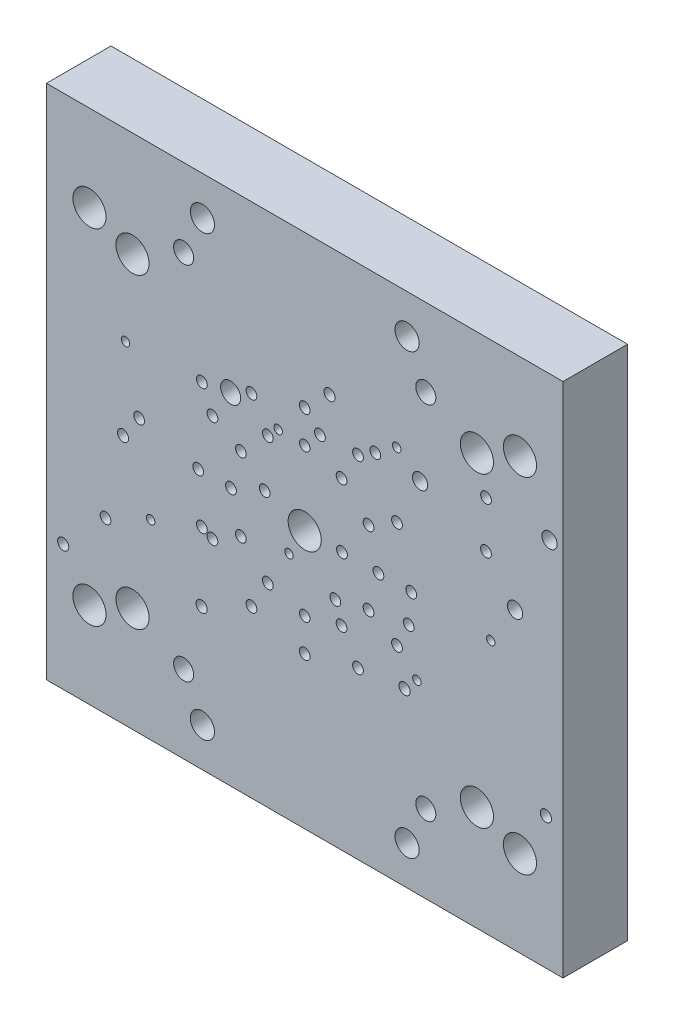
SolidWorks part; units mm, degrees
ref_plane "Front Plane" through (0, 0, 0) normal (0, 0, 1) x (1, 0, 0)
ref_plane "Top Plane" through (0, 0, 0) normal (0, 1, 0) x (1, 0, 0)
ref_plane "Right Plane" through (0, 0, 0) normal (1, 0, 0) x (0, 0, -1)
sketch "Sketch1" plane through (0, 0, 0) normal (0, 0, 1) x (1, 0, 0)
  line L1 (-152.4, 152.4) -> (152.4, 152.4)
  line L2 (-152.4, 152.4) -> (-152.4, -152.4)
  line L3 (-152.4, -152.4) -> (152.4, -152.4)
  line L4 (152.4, 152.4) -> (152.4, -152.4)
  line L5 (-152.4, 152.4) -> (152.4, -152.4) construction
  line L6 (-152.4, -152.4) -> (152.4, 152.4) construction
  point P0 (0, 0)
  dimension "D1" = 304.8
  dimension "D2" = 304.8
extrude "Boss-Extrude1" add sketch "Sketch1" along normal blind 38.1
sketch "Sketch2" plane through (0, 0, 38.1) normal (0, 0, 1) x (1, 0, 0)
  line L0 (-152.4, 0) -> (152.4, 0) construction
  line L5 (-152.4, 152.4) -> (-152.4, -152.4) construction
  line L6 (152.4, -152.4) -> (152.4, 152.4) construction
  line L7 (-152.4, -101.6) -> (152.4, -101.6) construction
  line L8 (-152.4, 101.6) -> (152.4, 101.6) construction
  line L9 (0, 101.6) -> (0, -101.6) construction
  line L10 (127, 101.6) -> (127, -101.6) construction
  line L11 (-127, 101.6) -> (-127, -101.6) construction
  circle A0 centre (-127, 101.6) radius 6.5151
  circle A1 centre (127, 101.6) radius 6.5151
  circle A2 centre (127, -101.6) radius 6.5151
  circle A3 centre (-127, -101.6) radius 6.5151
  circle A4 centre (0, 0) radius 6.5151
  dimension "D5" = 13.0302
  dimension "D1" = 101.6
  dimension "D2" = 101.6
  dimension "D3" = 127
  dimension "D4" = 127
extrude "HAAS T-Slot Holes" cut sketch "Sketch2" against normal through all
sketch "Sketch3" plane through (0, 0, 38.1) normal (0, 0, 1) x (1, 0, 0)
  circle A0 centre (-127, 101.6) radius 9.779
  circle A1 centre (127, 101.6) radius 9.779
  circle A2 centre (0, 0) radius 9.779
  circle A3 centre (127, -101.6) radius 9.779
  circle A4 centre (-127, -101.6) radius 9.779
  dimension "D1" = 19.558
extrude "HAAS Counter Bores" cut sketch "Sketch3" against normal offset from surface (22.225 mm away) 15.875 contours A0 | A1 | A2 | A3 | A4 up to face at (6.5151, 0, 0)
sketch "Sketch4" plane through (0, 0, 38.1) normal (0, 0, 1) x (1, 0, 0)
  line L0 (-127, 90.4875) -> (127, 90.4875) construction
  line L1 (-127, 30.1625) -> (127, 30.1625) construction
  line L2 (-127, 30.1625) -> (-127, -30.1625) construction
  line L3 (-127, -30.1625) -> (127, -30.1625) construction
  line L4 (127, 30.1625) -> (127, -30.1625) construction
  line L5 (-127, 30.1625) -> (127, -30.1625) construction
  line L6 (-127, -30.1625) -> (127, 30.1625) construction
  line L7 (-127, -90.4875) -> (127, -90.4875) construction
  line L8 (-101.6, 90.4875) -> (-101.6, 84.1375) construction
  line L9 (-101.6, -90.4875) -> (-101.6, -84.1375) construction
  line L10 (101.6, -90.4875) -> (101.6, -84.1375) construction
  line L11 (101.6, 90.4875) -> (101.6, 84.1375) construction
  circle A0 centre (-101.6, 90.4875) radius 6.5151
  circle A1 centre (101.6, 90.4875) radius 6.5151
  circle A2 centre (-101.6, -90.4875) radius 6.5151
  circle A3 centre (101.6, -90.4875) radius 6.5151
  point P0 (0, 0)
  dimension "D9" = 13.0302
  dimension "D1" = 60.325
  dimension "D2" = 254
  dimension "D5" = 203.2
  dimension "D6" = 25.4
  dimension "D7" = 203.2
  dimension "D8" = 6.35
  dimension "D3" = 60.325
  dimension "D4" = 60.325
extrude "Tormach T-Slot Holes" cut sketch "Sketch4" against normal through all
sketch "Sketch5" plane through (0, 0, 38.1) normal (0, 0, 1) x (1, 0, 0)
  circle A0 centre (-101.6, 90.4875) radius 9.779
  circle A1 centre (101.6, 90.4875) radius 9.779
  circle A2 centre (101.6, -90.4875) radius 9.779
  circle A3 centre (-101.6, -90.4875) radius 9.779
  dimension "D1" = 19.558
extrude "Tormach Counter bores" cut sketch "Sketch5" against normal up to surface (22.225 mm away) up to face at (-117.221, 101.6, 15.875)
sketch "Sketch6" plane through (0, 0, 38.1) normal (0, 0, 1) x (1, 0, 0)
  circle A0 centre (0, 0) radius 43.5 construction
  circle A1 centre (0, 43.5) radius 3.0734
  circle A2 centre (0, -43.5) radius 3.0734
  dimension "D1" = 87.0001
  dimension "D2" = 6.1468
extrude "Sprocket Locating Holes" cut sketch "Sketch6" against normal blind 6.35
sketch "Sketch7" plane through (0, 0, 38.1) normal (0, 0, 1) x (1, 0, 0)
  circle A0 centre (0, 0) radius 43.5 construction
  circle A2 centre (43.5, 0) radius 3.175
  circle A4 centre (37.6721, -21.75) radius 3.175
  circle A5 centre (21.75, -37.6721) radius 3.175
  circle A6 centre (0, -43.5) radius 3.175 [skipped]
  circle A7 centre (-21.75, -37.6721) radius 3.175
  circle A8 centre (-37.6721, -21.75) radius 3.175
  circle A9 centre (-43.5, 0) radius 3.175
  circle A10 centre (-37.6721, 21.75) radius 3.175
  circle A11 centre (-21.75, 37.6721) radius 3.175
  circle A12 centre (0, 43.5) radius 3.175 [skipped]
  circle A13 centre (21.75, 37.6721) radius 3.175
  circle A14 centre (37.6721, 21.75) radius 3.175
  point P31 (0, 0)
  dimension "D1" = 87.0001
  dimension "D2" = 6.35
  dimension "D3" = 12
extrude "Sprocket Mounting clearance holes" cut sketch "Sketch7" against normal blind 9.525
sketch "Sketch8" plane through (0, 0, 38.1) normal (0, 0, 1) x (1, 0, 0)
  line L1 (-71.4375, 106.4641) -> (71.4375, 106.4641) construction
  line L2 (-71.4375, 106.4641) -> (-71.4375, -106.4641) construction
  line L3 (-71.4375, -106.4641) -> (71.4375, -106.4641) construction
  line L4 (71.4375, 106.4641) -> (71.4375, -106.4641) construction
  line L5 (-71.4375, 106.4641) -> (71.4375, -106.4641) construction
  line L6 (-71.4375, -106.4641) -> (71.4375, 106.4641) construction
  circle A0 centre (-71.4375, 106.4641) radius 5.9182
  circle A1 centre (71.4375, 106.4641) radius 5.9182
  circle A2 centre (71.4375, -106.4641) radius 5.9182
  circle A3 centre (-71.4375, -106.4641) radius 5.9182
  point P0 (0, 0)
  dimension "D3" = 11.8364
  dimension "D1" = 142.875
  dimension "D2" = 212.9282
extrude "1/2-13 Tapped Holes" cut sketch "Sketch8" against normal blind 19.05
sketch "Sketch9" plane through (0, 0, 38.1) normal (0, 0, 1) x (1, 0, 0)
  circle A0 centre (-117.5189, -52.2876) radius 3.175
  circle A1 centre (-60.6634, -28.4101) radius 3.175
  circle A2 centre (-60.6634, 45.677) radius 3.175
  circle A3 centre (-23.6198, 8.6335) radius 3.175
  circle A4 centre (-97.707, 8.6335) radius 3.175
  circle A5 centre (18.0623, -26.1797) radius 3.175
  circle A6 centre (21.9762, 0) radius 3.175
  circle A7 centre (61.3833, -17.3739) radius 3.175
  circle A8 centre (106.976, 70.3959) radius 3.175
  circle A9 centre (106.976, 42.9004) radius 3.175
  circle A10 centre (144.4539, 67.4373) radius 4.5
  circle A11 centre (124.1092, 21.6131) radius 4.5
  circle A12 centre (68.0681, 59.3279) radius 4.5
  circle A13 centre (58.9353, -51.2652) radius 3.3
  circle A14 centre (-142.4923, -78.095) radius 3.3
  circle A15 centre (-105.7351, 43.7713) radius 2.5
  circle A16 centre (-90.8975, -39.8642) radius 2.5
  circle A17 centre (-9.2711, -16.3656) radius 2.5
  circle A18 centre (-15.6655, 43.8657) radius 2.5
  circle A20 centre (14.6267, 76.8405) radius 3.3
  circle A21 centre (8.9855, 53.4682) radius 3.175
  circle A22 centre (41.6559, 60.6579) radius 3.175
extrude "SSB Holes" cut sketch "Sketch9" against normal blind 19.05
ref_axis "Axis1" through (0, 0, 0) along (0, 0, 1)
sketch "Sketch10" plane through (0, 0, 38.1) normal (0, 0, 1) x (1, 0, 0)
  circle A0 centre (0, 0) radius 62.865 construction
  circle A1 centre (0, 62.865) radius 3.175
  circle A13 centre (31.4325, 54.4427) radius 3.175
  circle A14 centre (54.4427, 31.4325) radius 3.175
  circle A15 centre (62.865, 0) radius 3.175
  circle A16 centre (54.4427, -31.4325) radius 3.175
  circle A17 centre (31.4325, -54.4427) radius 3.175
  circle A18 centre (0, -62.865) radius 3.175
  circle A19 centre (-31.4325, -54.4427) radius 3.175
  circle A20 centre (-54.4427, -31.4325) radius 3.175
  circle A21 centre (-62.865, 0) radius 3.175
  circle A22 centre (-54.4427, 31.4325) radius 3.175
  circle A23 centre (-31.4325, 54.4427) radius 3.175
  point P30 (0, 0)
  point P56 (0, 0)
  dimension "D1" = 125.73
  dimension "D2" = 6.35
  dimension "D4" = 12
extrude "Sprocket Countersunk Holes" cut sketch "Sketch10" against normal blind 19.05
sketch "Sketch12" plane through (0, 0, 38.1) normal (0, 0, 1) x (1, 0, 0)
  circle A0 centre (-107.2144, -4.9977) radius 3.3
  circle A1 centre (-60.8212, -69.1392) radius 3.3
  circle A2 centre (142.3129, -74.567) radius 3.3
  circle A4 centre (54.3307, 69.7186) radius 2.4964
  circle A5 centre (109.7823, -1.2607) radius 2.5
  circle A6 centre (66.2094, -43.3332) radius 2.5
  circle A7 centre (-43.6886, 48.7489) radius 5.9182
  circle A8 centre (-71.4375, 106.4641) radius 5.9182 construction
extrude "DSB Holes" cut sketch "Sketch12" against normal blind 19.05
sketch "Brake Rotor Toe Clamp Holes" plane through (0, 0, 38.1) normal (0, 0, 1) x (1, 0, 0)
  line L0 (-55.0143, 117.9786) -> (55.0143, -117.9786) construction
  line L1 (55.0143, 117.9786) -> (-55.0143, -117.9786) construction
  line L2 (-55.0143, 117.9786) -> (-60.3816, 129.4887) construction
  line L3 (55.0143, 117.9786) -> (60.3816, 129.4887) construction
  line L4 (-55.0143, -117.9786) -> (-60.3816, -129.4887) construction
  line L5 (55.0143, -117.9786) -> (60.3816, -129.4887) construction
  line L6 (0, 0) -> (192.0367, 0) construction
  line L7 (0, 0) -> (-160.9096, 0) construction
  circle A0 centre (0, 0) radius 130.175 construction
  circle A6 centre (-60.3816, 129.4887) radius 7.1437
  circle A7 centre (60.3816, 129.4887) radius 7.1437
  circle A8 centre (60.3816, -129.4887) radius 7.1437
  circle A9 centre (-60.3816, -129.4887) radius 7.1437
  point P16 (0, 0)
  point P17 (0, 0)
  point P19 (55.0143, 117.9786)
  dimension "D1" = 260.35
  dimension "D2" = 14.2875
  dimension "D3" = 14.2875
  dimension "D4" = 14.2875
  dimension "D5" = 14.2875
  dimension "D6" = 12.7
  dimension "D7" = 12.7
  dimension "D8" = 12.7
  dimension "D9" = 12.7
  dimension "D10" = 65
  dimension "D11" = 65
extrude "Cut-Extrude1" cut sketch "Brake Rotor Toe Clamp Holes" against normal through all
